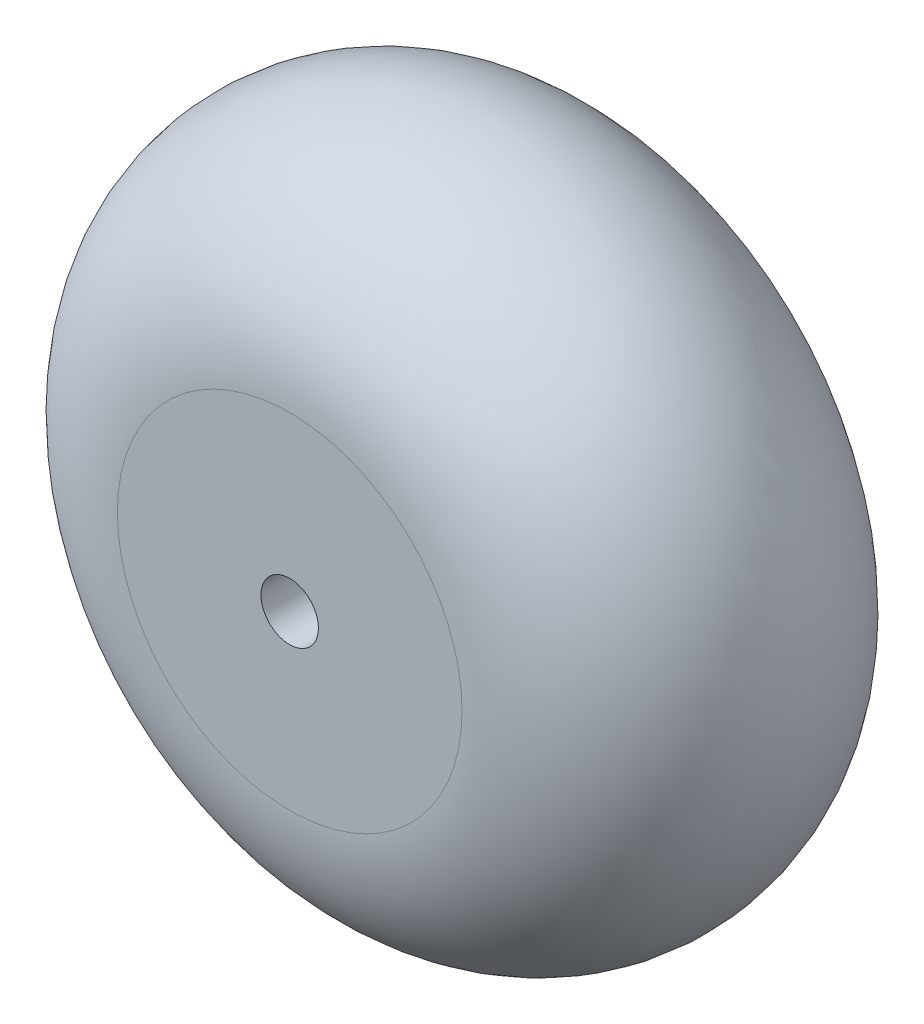
SolidWorks part; units mm, degrees
ref_plane "Front Plane" through (0, 0, 0) normal (0, 0, 1) x (1, 0, 0)
ref_plane "Top Plane" through (0, 0, 0) normal (0, 1, 0) x (1, 0, 0)
ref_plane "Right Plane" through (0, 0, 0) normal (1, 0, 0) x (0, 0, -1)
sketch "Sketch1" plane through (0, 0, 0) normal (0, 0, 1) x (1, 0, 0)
  circle A0 centre (0, 0) radius 30
  dimension "D1" = 60
extrude "Boss-Extrude1" add sketch "Sketch1" along normal blind 30
fillet "Fillet1" 2 edges at (30, 0, 0) (30, 0, 30) type full round first side face at (30, 0, 0) second side face at (30, 0, 30) middle face at (30, 0, 30)
sketch "Sketch2" plane through (0, 0, 0) normal (0, 0, -1) x (-1, 0, 0)
  circle A0 centre (0, 0) radius 2.5
  dimension "D1" = 5
extrude "Cut-Extrude1" cut sketch "Sketch2" against normal through all
